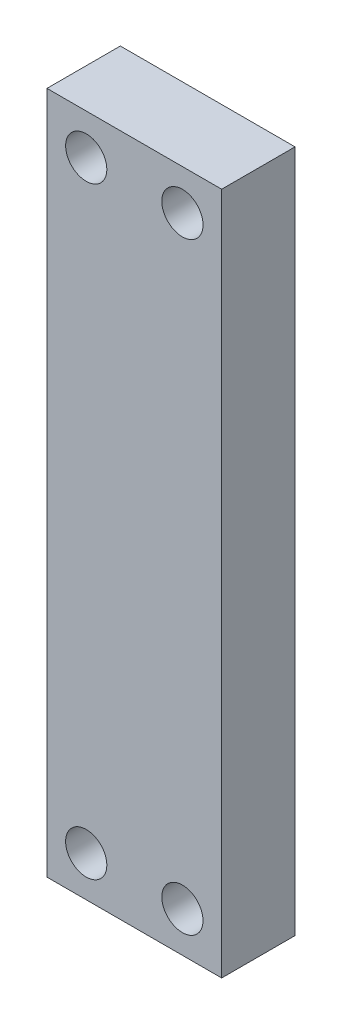
SolidWorks part; units mm, degrees
ref_plane "Front Plane" through (0, 0, 0) normal (0, 0, 1) x (1, 0, 0)
ref_plane "Top Plane" through (0, 0, 0) normal (0, 1, 0) x (1, 0, 0)
ref_plane "Right Plane" through (0, 0, 0) normal (1, 0, 0) x (0, 0, -1)
sketch "Sketch1" plane through (0, 0, 0) normal (0, 0, 1) x (1, 0, 0)
  line L1 (-9.525, 37.2491) -> (9.525, 37.2491)
  line L2 (-9.525, 37.2491) -> (-9.525, -37.2491)
  line L3 (-9.525, -37.2491) -> (9.525, -37.2491)
  line L4 (9.525, 37.2491) -> (9.525, -37.2491)
  line L5 (-9.525, 37.2491) -> (9.525, -37.2491) construction
  line L6 (-9.525, -37.2491) -> (9.525, 37.2491) construction
  point P0 (0, 0)
  dimension "D1" = 19.05
  dimension "D2" = 74.4982
extrude "Boss-Extrude1" add sketch "Sketch1" along normal blind 8.001
hole_wizard "#8 Clearance Hole1" positions "Sketch3" profile "Sketch2" hole size "#8" standard "ANSI Inch" end condition up to next
sketch "Sketch3" plane through (0, 0, 8.001) normal (0, 0, 1) x (1, 0, 0)
  line L1 (-5.2451, 32.8549) -> (5.2451, 32.8549) construction
  line L2 (-5.2451, 32.8549) -> (-5.2451, -32.8549) construction
  line L3 (-5.2451, -32.8549) -> (5.2451, -32.8549) construction
  line L4 (5.2451, 32.8549) -> (5.2451, -32.8549) construction
  line L5 (-5.2451, 32.8549) -> (5.2451, -32.8549) construction
  point P2 (-5.2451, 32.8549)
  point P3 (5.2451, -32.8549)
  point P274 (-5.2451, -32.8549)
  point P275 (5.2451, 32.8549)
  dimension "D1" = 10.4902
  dimension "D2" = 65.7098
sketch "Sketch2" plane through (-5.2451, 32.8549, 8.001) normal (1, 0, 0) x (0, -1, 0)
  line L0 (0, 0) -> (0, 8.001)
  line L1 (0, 8.001) -> (2.2479, 8.001)
  line L2 (2.2479, 8.001) -> (2.2479, 0)
  line L5 (2.2479, 0) -> (0, 0)
  line L11 (0, -6.35) -> (0, 107.95) construction
  dimension "Thru Hole Dia." = 4.4958
  dimension "Thru Hole Depth" = 8.001
